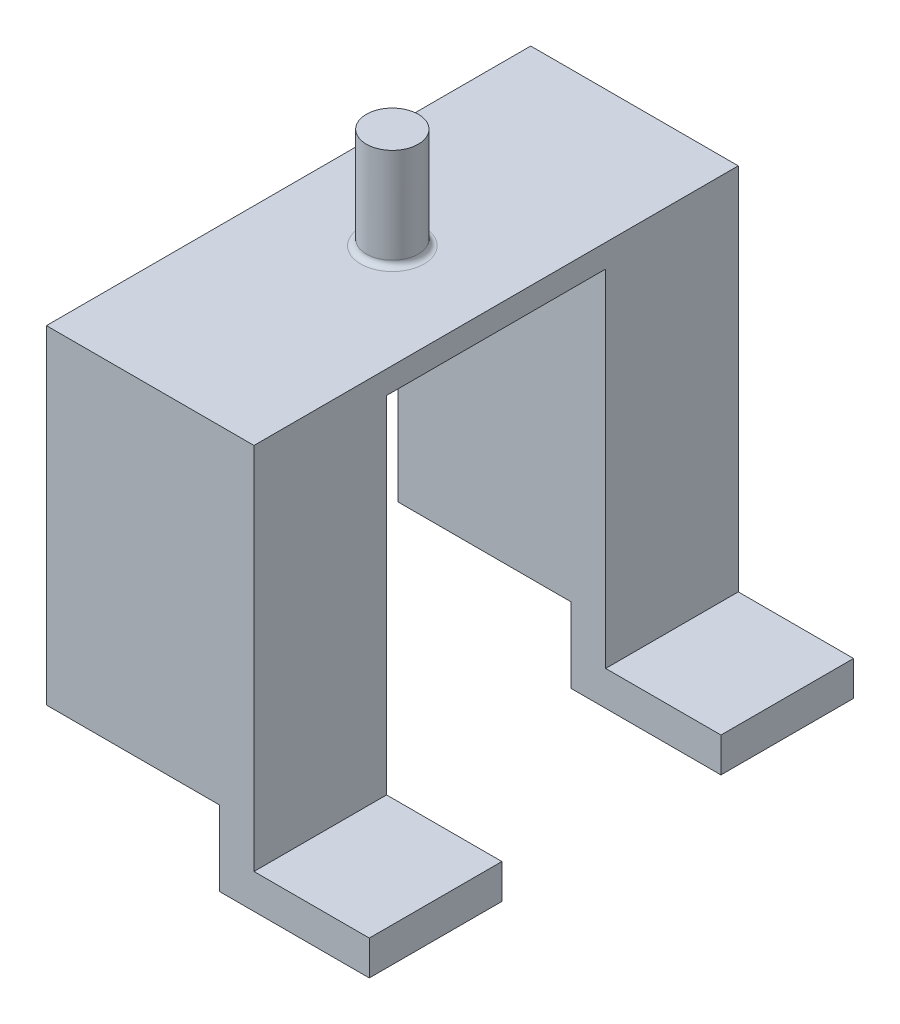
SolidWorks part; units mm, degrees
ref_plane "Front Plane" through (0, 0, 0) normal (0, 0, 1) x (1, 0, 0)
ref_plane "Top Plane" through (0, 0, 0) normal (0, 1, 0) x (1, 0, 0)
ref_plane "Right Plane" through (0, 0, 0) normal (1, 0, 0) x (0, 0, -1)
sketch "Sketch1" plane through (0, 0, 0) normal (0, 0, 1) x (1, 0, 0)
  line L1 (17.3768, 0) -> (17.3768, 6.5)
  line L2 (17.3768, 6.5) -> (2.3768, 6.5)
  line L3 (2.3768, 6.5) -> (2.3768, 35)
  line L8 (2.3768, 35) -> (20.3768, 35)
  line L11 (20.3768, 35) -> (20.3768, 3)
  line L12 (17.3768, 0) -> (30.3768, 0)
  line L13 (30.3768, 0) -> (30.3768, 3)
  line L14 (30.3768, 3) -> (20.3768, 3)
  point P0 (2.3768, 35)
  dimension "D1" = 6.5
  dimension "D2" = 35
  dimension "D3" = 3
  dimension "D4" = 3
  dimension "D7" = 15
  dimension "D8" = 10
extrude "Boss-Extrude1" add sketch "Sketch1" along normal blind 42
sketch "Sketch2" plane through (30.3768, 0, 0) normal (1, 0, 0) x (0, 0, -1)
  line L0 (-42, 0) -> (0, 0) construction
  line L1 (-11.5, 0) -> (-30.5, 0)
  line L2 (-11.5, 0) -> (-11.5, 33)
  line L3 (-11.5, 33) -> (-30.5, 33)
  line L4 (-30.5, 0) -> (-30.5, 33)
  line L5 (0, 19) -> (-42, 19) construction
  line L6 (0, 3) -> (0, 35) construction
  line L7 (-42, 3) -> (-42, 35) construction
  line L8 (-42, 19) -> (-42, 35) construction
  line L9 (-42, 35) -> (0, 0) construction
  line L10 (0, 0) -> (0, 35) construction
  line L11 (0, 35) -> (-42, 0) construction
  line L12 (-21, 17.5) -> (-21, 0) construction
  point P12 (-21, 0)
  dimension "D1" = 33
  dimension "D2" = 19
extrude "Cut-Extrude1" cut sketch "Sketch2" against normal up to surface (28 mm away) up to face at (2.3768, 20.75, 21)
ref_plane "Plane1" through (0, 0, 21) normal (0, 0, -1) x (-1, 0, 0)
sketch "Sketch3" plane through (0, 35, 0) normal (0, 1, 0) x (1, 0, 0)
  line L0 (15.4, -21) -> (-15.4, -21) construction
  line L2 (2.3768, -42) -> (2.3768, 0) construction
  circle A0 centre (11.3768, -21) radius 2.25
  dimension "D1" = 4.5
  dimension "D2" = 9
extrude "Boss-Extrude2" add sketch "Sketch3" along normal blind 8.75 contours A0
fillet "Fillet1" radius 0.5 1 edges at (11.3768, 35, 18.75)
